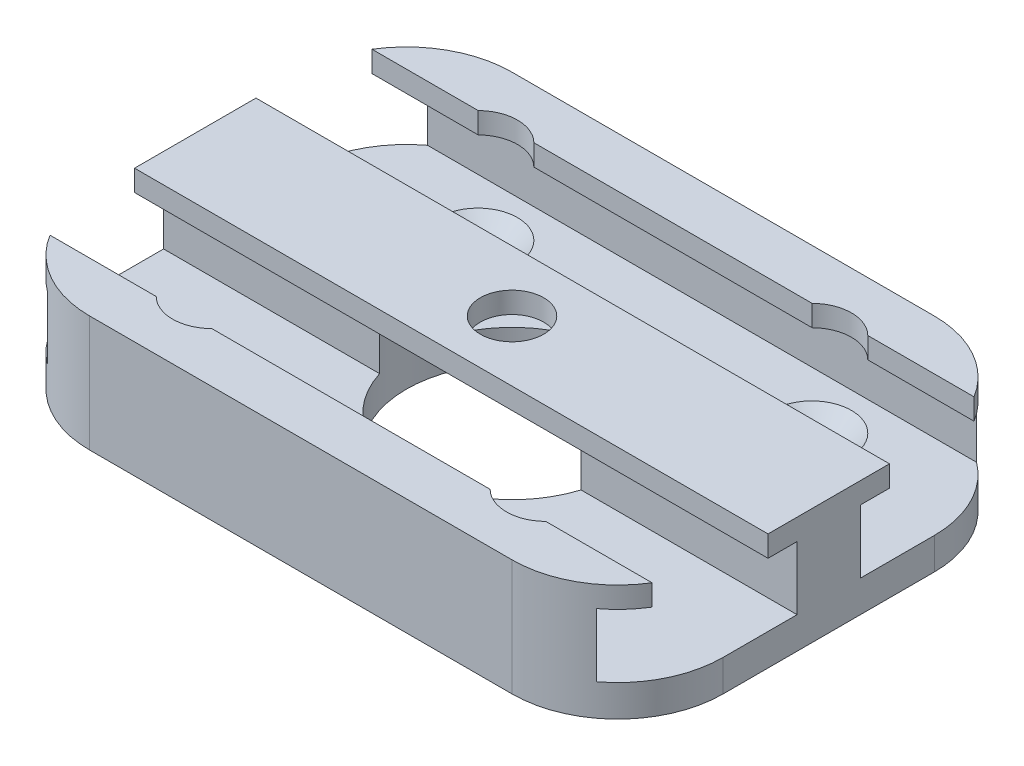
SolidWorks part; units mm, degrees
ref_plane "Front Plane" through (0, 0, 0) normal (0, 0, 1) x (1, 0, 0)
ref_plane "Top Plane" through (0, 0, 0) normal (0, 1, 0) x (1, 0, 0)
ref_plane "Right Plane" through (0, 0, 0) normal (1, 0, 0) x (0, 0, -1)
sketch "Sketch1" plane through (0, 0, 0) normal (0, 1, 0) x (1, 0, 0)
  line L0 (0, 20) -> (0, -20) construction
  line L1 (-30, -20) -> (30, -20)
  line L2 (-30, -20) -> (-30, 20)
  line L3 (-30, 20) -> (30, 20)
  line L4 (30, -20) -> (30, 20)
  line L5 (-30, -20) -> (30, 20) construction
  line L6 (-30, 20) -> (30, -20) construction
  line L7 (-30, 20) -> (30, 20)
  line L8 (-30, 20) -> (-30, 15.5)
  line L9 (-30, 15.5) -> (30, 15.5)
  line L10 (30, 20) -> (30, 15.5)
  line L11 (-30, -20) -> (30, -20)
  line L12 (-30, -20) -> (-30, -15.5)
  line L13 (-30, -15.5) -> (30, -15.5)
  line L14 (30, -20) -> (30, -15.5)
  line L15 (-30, 0) -> (30, 0) construction
  line L17 (-30, 6.25) -> (30, 6.25)
  line L18 (-30, 6.25) -> (-30, -6.25)
  line L19 (-30, -6.25) -> (30, -6.25)
  line L20 (30, 6.25) -> (30, -6.25)
  circle A0 centre (-15.5, 8) radius 1.75
  circle A1 centre (15.5, 8) radius 1.75
  circle A2 centre (15.5, -8) radius 1.75
  circle A3 centre (-15.5, -8) radius 1.75
  circle A4 centre (0, 0) radius 10
  circle A5 centre (0, 0) radius 3
  point P0 (0, 0)
  dimension "D3" = 3.5
  dimension "D4" = 14.5
  dimension "D5" = 12
  dimension "D7" = 20
  dimension "D8" = 6
  dimension "D1" = 40
  dimension "D2" = 60
  dimension "D6" = 4.5
extrude "Boss-Extrude1" add sketch "Sketch1" along normal blind 11 contours L13 L2 L1 L4 | A4 L19 A3 L2 L13 L4 A2 | A4 L17 L2 L19 | A4 L19 L4 L17 | A4 L17 A1 L4 L9 L2 A0 | L2 L9 L4 L3 | A4 | A0 | A2 | A1 | A3 region at (0, 0, 17.75) region at (0, 0, 11.242) region at (-19.6421, 0, 0) region at (19.6421, 0, 0) region at (0, 0, -11.242) region at (0, 0, -17.75)
sketch "Sketch3" plane through (-30, 0, 0) normal (-1, 0, 0) x (0, 0, 1)
  line L0 (0, 0) -> (0, 11) construction
  line L1 (-18, 9) -> (-3, 9)
  line L2 (-18, 9) -> (-18, 3)
  line L3 (-18, 3) -> (-3, 3)
  line L4 (-3, 9) -> (-3, 3)
  line L5 (20, 0) -> (-20, 0) construction
  line L6 (20, 11) -> (-20, 11) construction
  line L7 (-20, 11) -> (-20, 0) construction
  line L8 (18, 3) -> (3, 3)
  line L9 (3, 9) -> (3, 3)
  line L10 (18, 9) -> (3, 9)
  line L11 (18, 9) -> (18, 3)
  line L12 (-15.25, 9) -> (-5.75, 9)
  line L13 (-5.75, 9) -> (-5.75, 11)
  line L14 (-5.75, 11) -> (-15.25, 11)
  line L15 (-15.25, 11) -> (-15.25, 9)
  line L16 (5.75, 11) -> (15.25, 11)
  line L17 (5.75, 9) -> (5.75, 11)
  line L18 (15.25, 9) -> (5.75, 9)
  line L19 (15.25, 11) -> (15.25, 9)
  point P20 (-10.5, 9)
  dimension "D1" = 15
  dimension "D2" = 6
  dimension "D3" = 3
  dimension "D4" = 2
  dimension "D5" = 9.5
extrude "Cut-Extrude10" cut sketch "Sketch3" against normal through all contours L11 L10 L9 L8 | L1 L4 L3 L2 | L15 L12 L13 L14 | L16 L19 L18 L17 region at (-30, 6, 10.5)
hole_wizard "CSK for M3 Hex Socket Countersunk Cap Screw2" positions "3DSketch4" profile "Sketch7" countersink size "M3" standard "ISO" end condition through all
sketch3d "3DSketch4"
  line L0 (30, 0, 20) -> (30, 0, -20) construction
  line L1 (-30, 0, 20) -> (-30, 0, -20) construction
  line L2 (-30, 0, -20) -> (30, 0, -20) construction
  line L3 (-30, 0, 20) -> (30, 0, 20) construction
  point P0 (15.8137, 3, -12.5838)
  point P2 (15.8137, 3, 12.5838)
  point P4 (-15.8137, 3, 12.5838)
  point P6 (-15.8137, 3, -12.5838)
  dimension "D1" = 14.5
  dimension "D2" = 14.5
  dimension "D3" = 14.5
  dimension "D4" = 14.5
  dimension "D5" = 8
  dimension "D6" = 8
  dimension "D7" = 8
  dimension "D8" = 8
sketch "Sketch7" plane through (15.8137, 3, -12.5838) normal (1, 0, 0) x (0, 0, 1)
  line L0 (0, 0) -> (0, 3)
  line L1 (0, 3) -> (1.75, 3)
  line L2 (1.75, 3) -> (1.75, 2)
  line L3 (1.75, 2) -> (3.75, 0)
  line L5 (3.75, 0) -> (0, 0)
  line L6 (-1.75, 2) -> (-3.75, 0) construction
  line L11 (0, -6.35) -> (0, 107.95) construction
  dimension "Thru Hole Dia." = 3.5
  dimension "Thru Hole Depth" = 3
  dimension "Near C'Sink Dia." = 7.5
  dimension "Near C'Sink Angle" = 90
extrude "Cut-Extrude19" cut sketch "Sketch1<6>" along normal up to surface (9 mm away) contours A4 up to face at (0, 9, -4.375)
sketch "Sketch1<6>" plane through (0, 0, 0) normal (0, 1, 0) x (1, 0, 0) same geometry as "Sketch1"
extrude "Cut-Extrude21" cut sketch "Sketch1<7>" along direction (0, 1, 0) on the side against the normal through all from surface contours A5 starting at face at (0, 11, 0)
sketch "Sketch1<7>" plane through (0, 0, 0) normal (0, 1, 0) x (1, 0, 0) same geometry as "Sketch1"
sketch "Sketch8" plane through (0, 11, 0) normal (0, 1, 0) x (1, 0, 0)
  circle A0 centre (-15.8137, -12.5838) radius 3.75 construction
  circle A1 centre (15.8137, -12.5838) radius 3.75 construction
  circle A2 centre (15.8137, 12.5838) radius 3.75 construction
  circle A3 centre (-15.8137, 12.5838) radius 3.75 construction
  circle A4 centre (-15.8137, -12.5838) radius 3.75
  circle A5 centre (15.8137, -12.5838) radius 3.75
  circle A6 centre (15.8137, 12.5838) radius 3.75
  circle A7 centre (-15.8137, 12.5838) radius 3.75
extrude "Cut-Extrude22" cut sketch "Sketch8" against normal up to surface (2 mm away) up to face at (0, 9, -3)
fillet "Fillet1" radius 10 4 edges at (30, 5.5, -20) (30, 5.5, 20) (-30, 5.5, 20) (-30, 5.5, -20)
